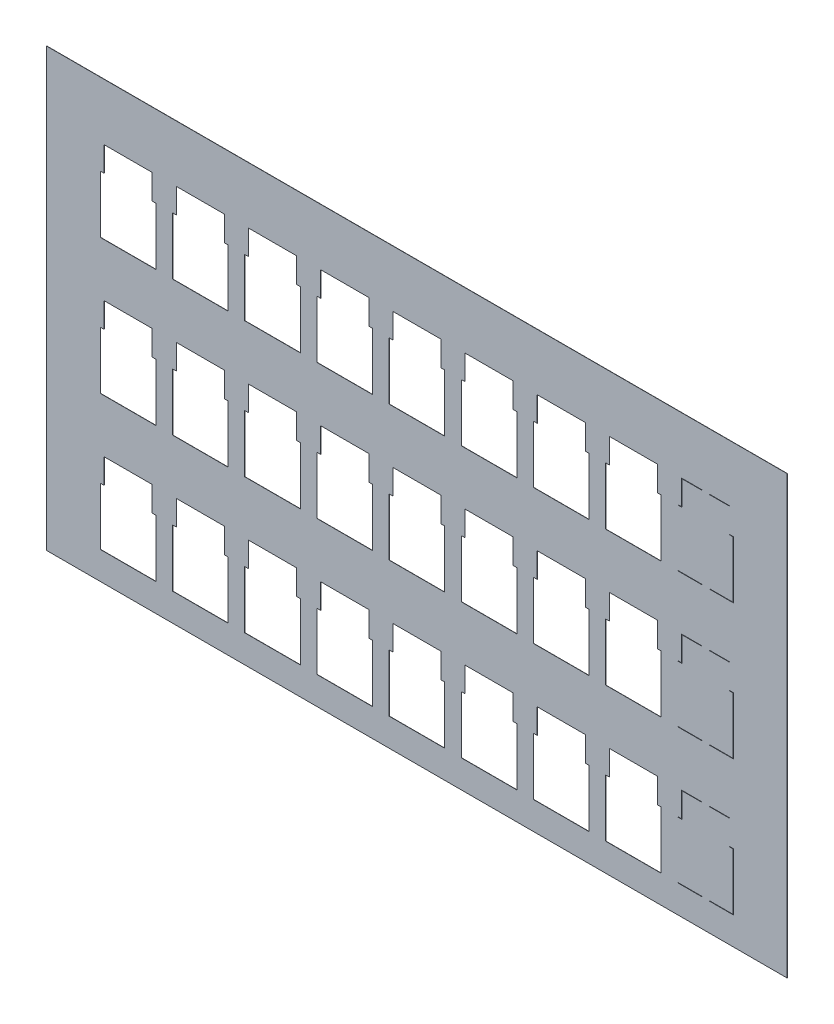
SolidWorks part; units mm, degrees
ref_plane "Front Plane" through (0, 0, 0) normal (0, 0, 1) x (1, 0, 0)
ref_plane "Top Plane" through (0, 0, 0) normal (0, 1, 0) x (1, 0, 0)
ref_plane "Right Plane" through (0, 0, 0) normal (1, 0, 0) x (0, 0, -1)
sketch "Model" plane through (0, 0, 0) normal (0, 0, 1) x (1, 0, 0)
  line L0 (1790, 440) -> (1640, 440)
  line L1 (1640, 440) -> (1640, 595)
  line L2 (1640, 595) -> (1650, 595)
  line L3 (1650, 595) -> (1650, 662)
  line L4 (1650, 662) -> (1780, 662)
  line L5 (1780, 662) -> (1780, 595)
  line L6 (1780, 595) -> (1790, 595)
  line L7 (1790, 595) -> (1790, 440)
  line L8 (1595, 440) -> (1445, 440)
  line L9 (1445, 440) -> (1445, 595)
  line L10 (1445, 595) -> (1455, 595)
  line L11 (1455, 595) -> (1455, 662)
  line L12 (1455, 662) -> (1585, 662)
  line L13 (1585, 662) -> (1585, 595)
  line L14 (1585, 595) -> (1595, 595)
  line L15 (1595, 595) -> (1595, 440)
  line L16 (1400, 440) -> (1250, 440)
  line L17 (1250, 440) -> (1250, 595)
  line L18 (1250, 595) -> (1260, 595)
  line L19 (1260, 595) -> (1260, 662)
  line L20 (1260, 662) -> (1390, 662)
  line L21 (1390, 662) -> (1390, 595)
  line L22 (1390, 595) -> (1400, 595)
  line L23 (1400, 595) -> (1400, 440)
  line L24 (1205, 440) -> (1055, 440)
  line L25 (1055, 440) -> (1055, 595)
  line L26 (1055, 595) -> (1065, 595)
  line L27 (1065, 595) -> (1065, 662)
  line L28 (1065, 662) -> (1195, 662)
  line L29 (1195, 662) -> (1195, 595)
  line L30 (1195, 595) -> (1205, 595)
  line L31 (1205, 595) -> (1205, 440)
  line L32 (1010, 440) -> (860, 440)
  line L33 (860, 440) -> (860, 595)
  line L34 (860, 595) -> (870, 595)
  line L35 (870, 595) -> (870, 662)
  line L36 (870, 662) -> (1000, 662)
  line L37 (1000, 662) -> (1000, 595)
  line L38 (1000, 595) -> (1010, 595)
  line L39 (1010, 595) -> (1010, 440)
  line L40 (815, 440) -> (665, 440)
  line L41 (665, 440) -> (665, 595)
  line L42 (665, 595) -> (675, 595)
  line L43 (675, 595) -> (675, 662)
  line L44 (675, 662) -> (805, 662)
  line L45 (805, 662) -> (805, 595)
  line L46 (805, 595) -> (815, 595)
  line L47 (815, 595) -> (815, 440)
  line L48 (620, 440) -> (470, 440)
  line L49 (470, 440) -> (470, 595)
  line L50 (470, 595) -> (480, 595)
  line L51 (480, 595) -> (480, 662)
  line L52 (480, 662) -> (610, 662)
  line L53 (610, 662) -> (610, 595)
  line L54 (610, 595) -> (620, 595)
  line L55 (620, 595) -> (620, 440)
  line L56 (425, 440) -> (275, 440)
  line L57 (275, 440) -> (275, 595)
  line L58 (275, 595) -> (285, 595)
  line L59 (285, 595) -> (285, 662)
  line L60 (285, 662) -> (415, 662)
  line L61 (415, 662) -> (415, 595)
  line L62 (415, 595) -> (425, 595)
  line L63 (425, 595) -> (425, 440)
  line L64 (230, 440) -> (80, 440)
  line L65 (80, 440) -> (80, 595)
  line L66 (80, 595) -> (90, 595)
  line L67 (90, 595) -> (90, 662)
  line L68 (90, 662) -> (220, 662)
  line L69 (220, 662) -> (220, 595)
  line L70 (220, 595) -> (230, 595)
  line L71 (230, 595) -> (230, 440)
  line L72 (1790, 805) -> (1640, 805)
  line L73 (1640, 805) -> (1640, 960)
  line L74 (1640, 960) -> (1650, 960)
  line L75 (1650, 960) -> (1650, 1027)
  line L76 (1650, 1027) -> (1780, 1027)
  line L77 (1780, 1027) -> (1780, 960)
  line L78 (1780, 960) -> (1790, 960)
  line L79 (1790, 960) -> (1790, 805)
  line L80 (1595, 805) -> (1445, 805)
  line L81 (1445, 805) -> (1445, 960)
  line L82 (1445, 960) -> (1455, 960)
  line L83 (1455, 960) -> (1455, 1027)
  line L84 (1455, 1027) -> (1585, 1027)
  line L85 (1585, 1027) -> (1585, 960)
  line L86 (1585, 960) -> (1595, 960)
  line L87 (1595, 960) -> (1595, 805)
  line L88 (1400, 805) -> (1250, 805)
  line L89 (1250, 805) -> (1250, 960)
  line L90 (1250, 960) -> (1260, 960)
  line L91 (1260, 960) -> (1260, 1027)
  line L92 (1260, 1027) -> (1390, 1027)
  line L93 (1390, 1027) -> (1390, 960)
  line L94 (1390, 960) -> (1400, 960)
  line L95 (1400, 960) -> (1400, 805)
  line L96 (1205, 805) -> (1055, 805)
  line L97 (1055, 805) -> (1055, 960)
  line L98 (1055, 960) -> (1065, 960)
  line L99 (1065, 960) -> (1065, 1027)
  line L100 (1065, 1027) -> (1195, 1027)
  line L101 (1195, 1027) -> (1195, 960)
  line L102 (1195, 960) -> (1205, 960)
  line L103 (1205, 960) -> (1205, 805)
  line L104 (1010, 805) -> (860, 805)
  line L105 (860, 805) -> (860, 960)
  line L106 (860, 960) -> (870, 960)
  line L107 (870, 960) -> (870, 1027)
  line L108 (870, 1027) -> (1000, 1027)
  line L109 (1000, 1027) -> (1000, 960)
  line L110 (1000, 960) -> (1010, 960)
  line L111 (1010, 960) -> (1010, 805)
  line L112 (815, 805) -> (665, 805)
  line L113 (665, 805) -> (665, 960)
  line L114 (665, 960) -> (675, 960)
  line L115 (675, 960) -> (675, 1027)
  line L116 (675, 1027) -> (805, 1027)
  line L117 (805, 1027) -> (805, 960)
  line L118 (805, 960) -> (815, 960)
  line L119 (815, 960) -> (815, 805)
  line L120 (620, 805) -> (470, 805)
  line L121 (470, 805) -> (470, 960)
  line L122 (470, 960) -> (480, 960)
  line L123 (480, 960) -> (480, 1027)
  line L124 (480, 1027) -> (610, 1027)
  line L125 (610, 1027) -> (610, 960)
  line L126 (610, 960) -> (620, 960)
  line L127 (620, 960) -> (620, 805)
  line L128 (425, 805) -> (275, 805)
  line L129 (275, 805) -> (275, 960)
  line L130 (275, 960) -> (285, 960)
  line L131 (285, 960) -> (285, 1027)
  line L132 (285, 1027) -> (415, 1027)
  line L133 (415, 1027) -> (415, 960)
  line L134 (415, 960) -> (425, 960)
  line L135 (425, 960) -> (425, 805)
  line L136 (230, 805) -> (80, 805)
  line L137 (80, 805) -> (80, 960)
  line L138 (80, 960) -> (90, 960)
  line L139 (90, 960) -> (90, 1027)
  line L140 (90, 1027) -> (220, 1027)
  line L141 (220, 1027) -> (220, 960)
  line L142 (220, 960) -> (230, 960)
  line L143 (230, 960) -> (230, 805)
  line L144 (1790, 75) -> (1640, 75)
  line L145 (1640, 75) -> (1640, 230)
  line L146 (1640, 230) -> (1650, 230)
  line L147 (1650, 230) -> (1650, 297)
  line L148 (1650, 297) -> (1780, 297)
  line L149 (1780, 297) -> (1780, 230)
  line L150 (1780, 230) -> (1790, 230)
  line L151 (1790, 230) -> (1790, 75)
  line L152 (1595, 75) -> (1445, 75)
  line L153 (1445, 75) -> (1445, 230)
  line L154 (1445, 230) -> (1455, 230)
  line L155 (1455, 230) -> (1455, 297)
  line L156 (1455, 297) -> (1585, 297)
  line L157 (1585, 297) -> (1585, 230)
  line L158 (1585, 230) -> (1595, 230)
  line L159 (1595, 230) -> (1595, 75)
  line L160 (1400, 75) -> (1250, 75)
  line L161 (1250, 75) -> (1250, 230)
  line L162 (1250, 230) -> (1260, 230)
  line L163 (1260, 230) -> (1260, 297)
  line L164 (1260, 297) -> (1390, 297)
  line L165 (1390, 297) -> (1390, 230)
  line L166 (1390, 230) -> (1400, 230)
  line L167 (1400, 230) -> (1400, 75)
  line L168 (1205, 75) -> (1055, 75)
  line L169 (1055, 75) -> (1055, 230)
  line L170 (1055, 230) -> (1065, 230)
  line L171 (1065, 230) -> (1065, 297)
  line L172 (1065, 297) -> (1195, 297)
  line L173 (1195, 297) -> (1195, 230)
  line L174 (1195, 230) -> (1205, 230)
  line L175 (1205, 230) -> (1205, 75)
  line L176 (1010, 75) -> (860, 75)
  line L177 (860, 75) -> (860, 230)
  line L178 (860, 230) -> (870, 230)
  line L179 (870, 230) -> (870, 297)
  line L180 (870, 297) -> (1000, 297)
  line L181 (1000, 297) -> (1000, 230)
  line L182 (1000, 230) -> (1010, 230)
  line L183 (1010, 230) -> (1010, 75)
  line L184 (815, 75) -> (665, 75)
  line L185 (665, 75) -> (665, 230)
  line L186 (665, 230) -> (675, 230)
  line L187 (675, 230) -> (675, 297)
  line L188 (675, 297) -> (805, 297)
  line L189 (805, 297) -> (805, 230)
  line L190 (805, 230) -> (815, 230)
  line L191 (815, 230) -> (815, 75)
  line L192 (620, 75) -> (470, 75)
  line L193 (470, 75) -> (470, 230)
  line L194 (470, 230) -> (480, 230)
  line L195 (480, 230) -> (480, 297)
  line L196 (480, 297) -> (610, 297)
  line L197 (610, 297) -> (610, 230)
  line L198 (610, 230) -> (620, 230)
  line L199 (620, 230) -> (620, 75)
  line L200 (425, 75) -> (275, 75)
  line L201 (275, 75) -> (275, 230)
  line L202 (275, 230) -> (285, 230)
  line L203 (285, 230) -> (285, 297)
  line L204 (285, 297) -> (415, 297)
  line L205 (415, 297) -> (415, 230)
  line L206 (415, 230) -> (425, 230)
  line L207 (425, 230) -> (425, 75)
  line L208 (230, 75) -> (80, 75)
  line L209 (80, 75) -> (80, 230)
  line L210 (80, 230) -> (90, 230)
  line L211 (90, 230) -> (90, 297)
  line L212 (90, 297) -> (220, 297)
  line L213 (220, 297) -> (220, 230)
  line L214 (220, 230) -> (230, 230)
  line L215 (230, 230) -> (230, 75)
  line L216 (0, 1180) -> (0, 0)
  line L217 (0, 0) -> (1870, 0)
  line L218 (1870, 0) -> (1870, 1180)
  line L219 (1870, 1180) -> (0, 1180)
  dimension "D1" = 3
base flange "Base-Flange1" sketch "Model" thickness 0.6 reverse thickness direction no parameters "D1"=0.7366
sketch "Sketch6" plane through (0, 0, 0) normal (0, 0, 1) x (1, 0, 0)
  line L3 (1705, 805) -> (1725, 805)
  line L7 (1725, 1027) -> (1705, 1027)
  line L8 (1779, 1026) -> (1725, 1026)
  line L9 (1651, 1026) -> (1651, 959)
  line L10 (1651, 959) -> (1641, 959)
  line L11 (1641, 959) -> (1641, 806)
  line L12 (1641, 806) -> (1705, 806)
  line L13 (1789, 806) -> (1789, 959)
  line L14 (1789, 959) -> (1779, 959)
  line L15 (1779, 959) -> (1779, 1026)
  line L16 (1705, 1026) -> (1651, 1026)
  line L17 (1780, 1027) -> (1650, 1027) construction
  line L18 (1705, 1027) -> (1705, 1026)
  line L19 (1725, 1027) -> (1725, 1026)
  line L20 (1705, 806) -> (1705, 805)
  line L21 (1725, 806) -> (1725, 805)
  line L22 (1725, 806) -> (1789, 806)
  line L23 (1641, 806) -> (1789, 806) construction
  line L24 (1779, 1026) -> (1651, 1026) construction
  line L25 (1640, 805) -> (1790, 805) construction
  line L26 (1650, 1027) -> (1650, 960) construction
  line L27 (1650, 960) -> (1640, 960) construction
  line L28 (1640, 960) -> (1640, 805) construction
  line L29 (1790, 805) -> (1790, 960) construction
  line L30 (1790, 960) -> (1780, 960) construction
  line L31 (1780, 960) -> (1780, 1027) construction
  line L32 (1705, 440) -> (1725, 440)
  line L33 (1725, 662) -> (1705, 662)
  line L34 (1779, 661) -> (1725, 661)
  line L35 (1651, 661) -> (1651, 594)
  line L36 (1651, 594) -> (1641, 594)
  line L37 (1641, 594) -> (1641, 441)
  line L38 (1641, 441) -> (1705, 441)
  line L39 (1789, 441) -> (1789, 594)
  line L40 (1789, 594) -> (1779, 594)
  line L41 (1779, 594) -> (1779, 661)
  line L42 (1705, 661) -> (1651, 661)
  line L43 (1705, 662) -> (1705, 661)
  line L44 (1725, 662) -> (1725, 661)
  line L45 (1705, 441) -> (1705, 440)
  line L46 (1725, 441) -> (1725, 440)
  line L47 (1725, 441) -> (1789, 441)
  line L48 (1705, 75) -> (1725, 75)
  line L49 (1725, 297) -> (1705, 297)
  line L50 (1779, 296) -> (1725, 296)
  line L51 (1651, 296) -> (1651, 229)
  line L52 (1651, 229) -> (1641, 229)
  line L53 (1641, 229) -> (1641, 76)
  line L54 (1641, 76) -> (1705, 76)
  line L55 (1789, 76) -> (1789, 229)
  line L56 (1789, 229) -> (1779, 229)
  line L57 (1779, 229) -> (1779, 296)
  line L58 (1705, 296) -> (1651, 296)
  line L59 (1705, 297) -> (1705, 296)
  line L60 (1725, 297) -> (1725, 296)
  line L61 (1705, 76) -> (1705, 75)
  line L62 (1725, 76) -> (1725, 75)
  line L63 (1725, 76) -> (1789, 76)
  dimension "D1" = 1
  dimension "D2" = 3
base flange "Tab1" sketch "Sketch6" thickness 0.6 reverse thickness direction no parameters "D1"=0.7366
sketch "Sketch7" plane through (0, 0, 0) normal (0, 0, 1) x (1, 0, 0)
  line L1 (1870, 1180) -> (1935, 1180)
  line L2 (1870, 1180) -> (1870, 0)
  line L3 (1870, 0) -> (1935, 0)
  line L4 (1935, 1180) -> (1935, 0)
  line L5 (0, 0) -> (-65, 0)
  line L6 (0, 0) -> (0, 1180)
  line L7 (0, 1180) -> (-65, 1180)
  line L8 (-65, 0) -> (-65, 1180)
  dimension "D1" = 65
  dimension "D2" = 65
base flange "Tab2" sketch "Sketch7" thickness 0.6 reverse thickness direction no parameters "D1"=0.7366
sketch "Bend-Lines1" [suppressed] plane through (0, 0, 0) normal (0, 1, 0) x (1, 0, 0)
sketch "Bounding-Box1" [suppressed] plane through (0, 0, 0) normal (0, 1, 0) x (1, 0, 0)
sheet metal parameters "Sheet-Metal1" thickness 0.6 parameters "D1"=0.7366
flat pattern "Flat-Pattern1" [suppressed]
sketch "Bend-Lines2" plane through (0, 0, 0) normal (0, 1, 0) x (1, 0, 0)
sketch3d "Bounding-Box2" [suppressed]
  line L0 (0, 0, 0) -> (-1870, 0, 0) construction
  line L1 (0, 1180, 0) -> (-1870, 1180, 0) construction
  line L2 (0, 0, 0) -> (0, 1180, 0) construction
  line L3 (-1870, 0, 0) -> (-1870, 1180, 0) construction
sheet metal parameters "Sheet-Metal2" thickness 0.6 parameters "D1"=0.7366
flat pattern "Flat-Pattern2"
sketch "Bend-Lines3" plane through (0, 0, 0) normal (0, 1, 0) x (1, 0, 0)
sketch3d "Bounding-Box3" [suppressed]
  line L0 (0, 0, 0) -> (-1870, 0, 0) construction
  line L1 (0, 1180, 0) -> (-1870, 1180, 0) construction
  line L2 (0, 0, 0) -> (0, 1180, 0) construction
  line L3 (-1870, 0, 0) -> (-1870, 1180, 0) construction
sheet metal parameters "Sheet-Metal5" thickness 0.6 parameters "D1"=0.7366
flat pattern "Flat-Pattern5"
sketch "Bend-Lines4" plane through (0, 0, 0) normal (0, 1, 0) x (1, 0, 0)
sketch3d "Bounding-Box4" [suppressed]
  line L0 (65, 0, 0) -> (-1935, 0, 0) construction
  line L1 (65, 1180, 0) -> (-1935, 1180, 0) construction
  line L2 (65, 0, 0) -> (65, 1180, 0) construction
  line L3 (-1935, 0, 0) -> (-1935, 1180, 0) construction
